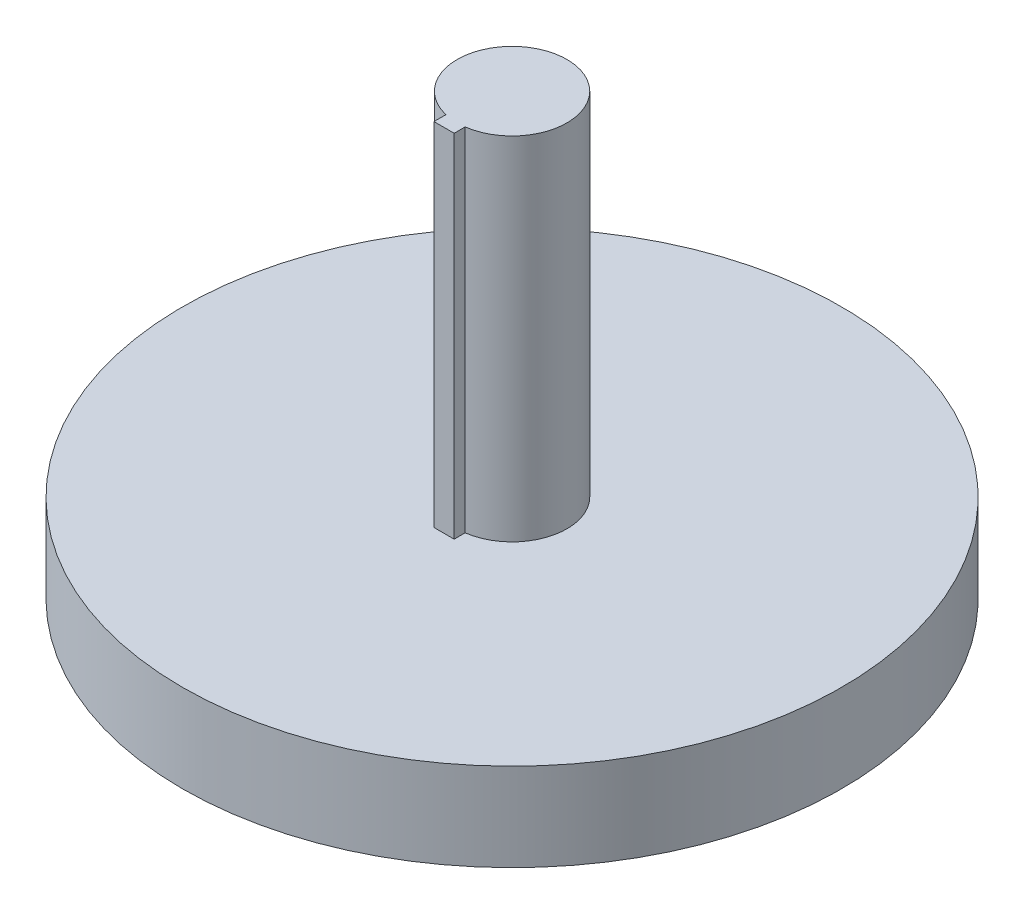
SolidWorks part; units mm, degrees
ref_plane "Front Plane" through (0, 0, 0) normal (0, 0, 1) x (1, 0, 0)
ref_plane "Top Plane" through (0, 0, 0) normal (0, 1, 0) x (1, 0, 0)
ref_plane "Right Plane" through (0, 0, 0) normal (1, 0, 0) x (0, 0, -1)
sketch "Sketch1" plane through (0, 0, 0) normal (0, 1, 0) x (1, 0, 0)
  line L1 (-5.7909, 2.0003) -> (3.4091, 2.0003)
  line L2 (-5.7909, 2.0003) -> (-5.7909, -29.7601)
  line L3 (-5.7909, -29.7601) -> (3.4091, -29.7601)
  line L4 (3.4091, 2.0003) -> (3.4091, -29.7601)
  line L5 (-5.7909, 2.0003) -> (3.4091, -29.7601) construction
  line L6 (-5.7909, -29.7601) -> (3.4091, 2.0003) construction
  circle A0 centre (0, 0) radius 150
  circle A1 centre (0, 0) radius 25
  point P4 (-1.1909, -13.8799)
  point P9 (3.4091, -24.7665)
  point P10 (-5.7909, -24.3201)
  point P11 (0, 0)
  point P12 (0, 0)
  point P13 (0, 0)
  dimension "D1" = 50
  dimension "D2" = 300
  dimension "D3" = 25
  dimension "D4" = 5.44
  dimension "D5" = 9.2
extrude "Boss-Extrude1" add sketch "Sketch1" along normal blind 40 contours A0 A1 L4 L3 L2 region at (-145.7574, 0, 0)
extrude "Boss-Extrude2" add sketch "Sketch1<3>" along normal blind 200 contours L4 A1 L2 L1 | L3 L4 L1 L2 region at (-6.4964, 0, 11.1599)
sketch "Sketch1<3>" plane through (0, 0, 0) normal (0, 1, 0) x (1, 0, 0) same geometry as "Sketch1"
